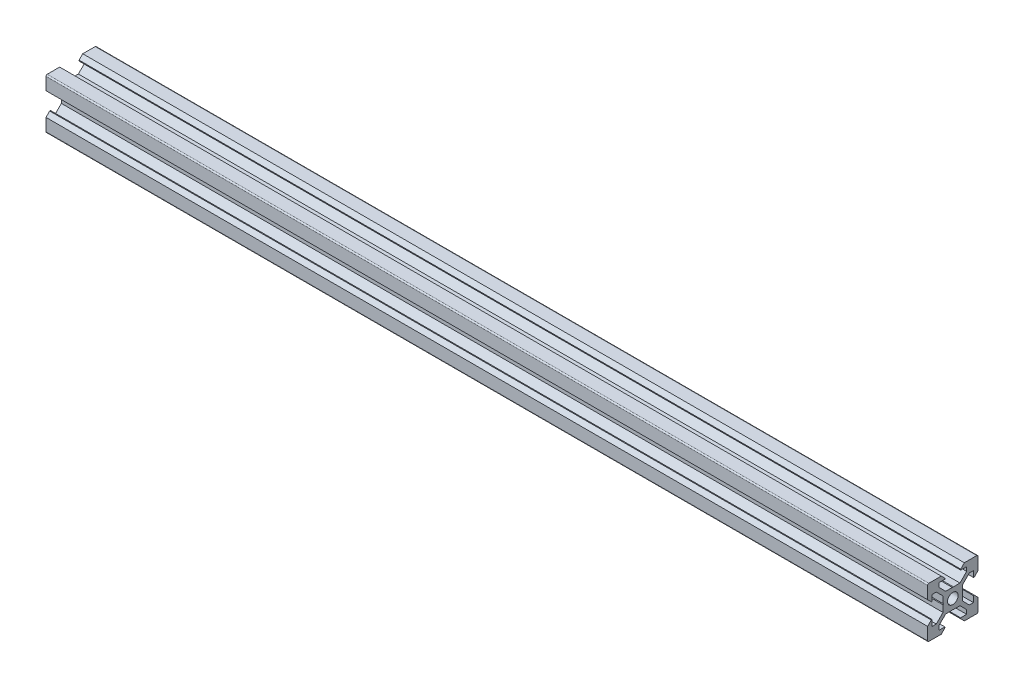
SolidWorks part; units mm, degrees
material "6061-T6 (SS)"
ref_plane "Top" through (0, 0, 0) normal (0, 0, 1) x (1, 0, 0)
ref_plane "Front" through (0, 0, 0) normal (0, 1, 0) x (1, 0, 0)
ref_plane "Right" through (0, 0, 0) normal (1, 0, 0) x (0, 0, -1)
sketch "Profile Sketch" plane through (0, 0, 0) normal (1, 0, 0) x (0, 0, -1)
  line L0 (-0.5, 10) -> (-5.42, 10)
  line L1 (-4.5, 8.2) -> (-4.5, 6.56)
  line L2 (-4.5, 6.56) -> (-7.16, 3.9)
  line L3 (-7.16, 3.9) -> (-9.79, 3.9)
  line L4 (-9.79, 3.9) -> (-10, 3.69)
  line L7 (-3.4387, 5.5) -> (-6.1, 2.8387)
  line L8 (-6.1, 2.8387) -> (-6.1, -0.21)
  line L9 (-6.875, 8.545) -> (-6.875, 8.2)
  line L10 (-6.875, 8.2) -> (-4.5, 8.2)
  line L11 (-6.875, 8.545) -> (-5.42, 10)
  line L12 (0, -10) -> (0, 10) construction
  line L13 (-20, 0) -> (20, 0) construction
  line L14 (-10, -10) -> (-10, 10) construction
  line L15 (-6.875, -8.545) -> (-5.42, -10)
  line L16 (-6.875, -8.2) -> (-4.5, -8.2)
  line L17 (-6.875, -8.545) -> (-6.875, -8.2)
  line L18 (-3.44, -5.5) -> (-6.1, -2.8387)
  line L21 (-7.16, -3.9) -> (-9.79, -3.9)
  line L22 (-4.5, -6.56) -> (-7.16, -3.9)
  line L23 (-4.5, -8.2) -> (-4.5, -6.56)
  line L24 (-0.5, -10) -> (-5.42, -10)
  line L25 (-10, 0) -> (-20, 10) construction
  line L26 (-18.545, 3.125) -> (-18.2, 3.125)
  line L27 (-13.125, -8.545) -> (-13.125, -8.2)
  line L28 (-13.125, -8.2) -> (-15.5, -8.2)
  line L29 (-13.125, -8.545) -> (-14.58, -10)
  line L30 (-15.5, -8.2) -> (-15.5, -6.56)
  line L31 (-15.5, -6.56) -> (-12.84, -3.9)
  line L32 (-12.84, -3.9) -> (-10.21, -3.9)
  line L33 (-20, 4.58) -> (-20, 9.5)
  line L34 (-13.9, 2.8387) -> (-13.9, 0.21)
  line L35 (-16.56, 5.5) -> (-13.9, 2.8387)
  line L36 (-12.84, 3.9) -> (-10.21, 3.9)
  line L37 (-15.5, 6.56) -> (-12.84, 3.9)
  line L38 (-15.5, 8.2) -> (-15.5, 6.56)
  line L39 (-13.125, 8.545) -> (-14.58, 10)
  line L40 (-13.125, 8.2) -> (-15.5, 8.2)
  line L41 (-13.125, 8.545) -> (-13.125, 8.2)
  line L42 (-18.2, 3.125) -> (-18.2, 5.5)
  line L43 (-18.545, 3.125) -> (-20, 4.58)
  line L44 (-18.2, 5.5) -> (-16.56, 5.5)
  line L45 (-14.58, 10) -> (-19.5, 10)
  line L46 (-16.56, -5.5) -> (-13.9, -2.8387)
  line L47 (-14.58, -10) -> (-19.5, -10)
  line L48 (-18.2, -5.5) -> (-16.56, -5.5)
  line L49 (-18.545, -3.125) -> (-20, -4.58)
  line L50 (-18.2, -3.125) -> (-18.2, -5.5)
  line L51 (-20, -4.58) -> (-20, -9.5)
  line L52 (-18.545, -3.125) -> (-18.2, -3.125)
  line L53 (10, -10) -> (10, 10) construction
  line L99 (-10, 3.69) -> (-10.21, 3.9)
  line L100 (-10, -3.69) -> (-10.21, -3.9)
  line L101 (-9.79, -3.9) -> (-10, -3.69)
  line L102 (-13.9, -0.21) -> (-13.69, 0)
  line L103 (-13.69, 0) -> (-13.9, 0.21)
  line L104 (-13.9, -0.21) -> (-13.9, -2.8387)
  line L105 (-6.1, -0.21) -> (-6.31, 0)
  line L106 (-6.31, 0) -> (-6.1, -0.21)
  line L107 (-6.1, -0.21) -> (-6.1, -2.8387)
  line L117 (-5.42, -10) -> (-0.5, -10)
  line L118 (20, -10) -> (20, 10) construction
  line L119 (20, -10) -> (-20, -10) construction
  line L120 (-20, -10) -> (-20, 10) construction
  line L121 (20, 10) -> (-20, 10) construction
  line L122 (20, -10) -> (-20, 10) construction
  line L123 (-20, -10) -> (20, 10) construction
  line L124 (-5.42, 10) -> (-0.5, 10)
  line L125 (-1.455, 3.125) -> (-1.8, 3.125)
  line L126 (-1.455, -3.125) -> (-1.8, -3.125)
  line L127 (-1.8, -5.5) -> (-3.44, -5.5)
  line L128 (-1.8, 5.5) -> (-3.44, 5.5)
  line L129 (-1.8, 3.125) -> (-1.8, 5.5)
  line L130 (-1.8, -3.125) -> (-1.8, -5.5)
  line L131 (0, -4.58) -> (0, -9.5)
  line L132 (0, 4.58) -> (0, 9.5)
  line L133 (-1.455, 3.125) -> (0, 4.58)
  line L134 (-1.455, -3.125) -> (0, -4.58)
  circle A0 centre (-10, 0) radius 2.1
  arc A1 (-19.5, 10) -> (-20, 9.5) centre (-19.5, 9.5) ccw
  arc A2 (-19.5, -10) -> (-20, -9.5) centre (-19.5, -9.5) cw
  arc A3 (-0.5, -10) -> (0, -9.5) centre (-0.5, -9.5) ccw
  arc A4 (-0.5, 10) -> (0, 9.5) centre (-0.5, 9.5) cw
  point P2 (-17.38, 5.5)
  point P35 (-2.4957, 0)
  point P76 (-2.62, 5.5)
  point P108 (0, -8.2)
  point P119 (0, 8.2)
  point P131 (0, 0)
  point P143 (0, 0)
  dimension "D4" = 5.42
  dimension "D5" = 40
  dimension "D6" = 4.2
  dimension "D16" = 0.5
  dimension "D1" = 0.21
  dimension "D2" = 45
  dimension "D3" = 20
  dimension "D7" = 1.5
  dimension "D8" = 1.8
  dimension "D9" = 10
  dimension "D10" = 3.9
  dimension "D11" = 3.9
  dimension "D13" = 3.125
  dimension "D14" = 5.5
  dimension "D15" = 1.64
extrude "Profile Extrude" add sketch "Profile Sketch" along normal blind 350 contours L126 L0 L11 L9 L10 L1 L2 L3 L4 L99 L36 L37 L38 L40 L41 L39 L45 A1 L33 L43 L26 L42 L44 L35 L34 L103 L102 L104 L46 L48 L50 L52 L49 L51 A2 L47 region at (0, 9.6536, 0.3464)
equation "\"M2x0.4_Close_Hole\"= 2.2"
equation "\"M2.5x0.45_Close_Hole\"= 2.7"
equation "\"M3x0.5_Close_Hole\"= 3.2"
equation "\"M4x0.7_Close_Hole\"= 4.3"
equation "\"M5x0.8_Close_Hole\"= 5.3"
equation "\"M6x1_Close_Hole\"= 6.3"
equation "\"M7x1_Close_Hole\"= 7.4"
equation "\"M8x1.25_Close_Hole\"= 8.4"
equation "\"M2x0.4_Tap_Hole_75\"= 1.6"
equation "\"M3x0.5_Tap_Hole_75\"= 2.5"
equation "\"M4x0.7_Tap_Hole_75\"= 3.3"
equation "\"M5x0.8_Tap_Hole_75\"= 4.2"
equation "\"M6x1_Tap_Hole_75\"= 5"
equation "\"M7x1_Tap_Hole_75\"= 6"
equation "\"M8x1.25_Tap_Hole_75\"= 6.8"
